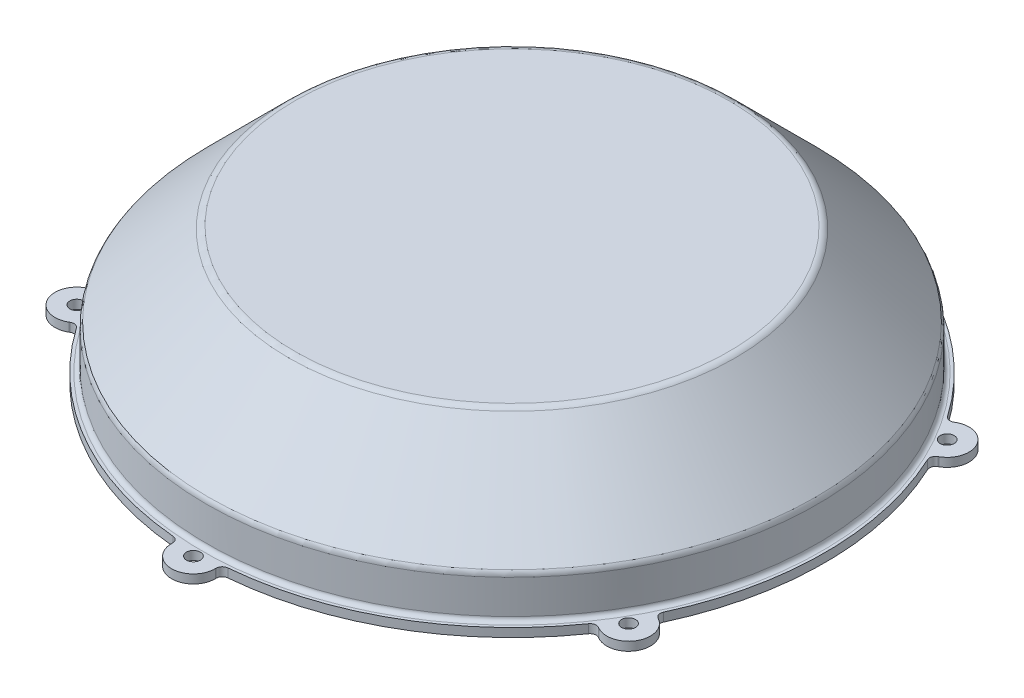
SolidWorks part; units mm, degrees
material "АБС-2020, черный"
ref_plane "Спереди" through (0, 0, 0) normal (0, 0, 1) x (1, 0, 0)
ref_plane "Сверху" through (0, 0, 0) normal (0, 1, 0) x (1, 0, 0)
ref_plane "Справа" through (0, 0, 0) normal (1, 0, 0) x (0, 0, -1)
other "Configuration Table"
sketch "Эскиз1" plane through (0, 0, 0) normal (0, 1, 0) x (1, 0, 0)
  circle A0 centre (0, 0) radius 70
  circle A1 centre (0, 0) radius 67.5
  dimension "D1" = 140
  dimension "D2" = 135
extrude "Бобышка-Вытянуть1" add sketch "Эскиз1" along normal blind 10
sketch "Эскиз2" plane through (0, 0, 0) normal (0, -1, 0) x (1, 0, 0)
  line L0 (0, 0) -> (0, 68.2261) construction
  line L1 (-5, 73) -> (-5, 72.7838)
  line L2 (60.7199, 40.8301) -> (60.5327, 40.722)
  line L3 (5, 72.7838) -> (5, 73)
  line L4 (0, 69.7236) -> (0, 91.161) construction
  line L5 (65.5327, 32.0618) -> (65.7199, 32.1699)
  line L6 (65.7199, -32.1699) -> (65.5327, -32.0618)
  line L7 (60.5327, -40.722) -> (60.7199, -40.8301)
  line L8 (5, -73) -> (5, -72.7838)
  line L9 (-5, -72.7838) -> (-5, -73)
  line L10 (-60.7199, -40.8301) -> (-60.5327, -40.722)
  line L11 (-65.5327, -32.0618) -> (-65.7199, -32.1699)
  line L12 (-65.7199, 32.1699) -> (-65.5327, 32.0618)
  line L13 (-60.5327, 40.722) -> (-60.7199, 40.8301)
  arc A0 (5, 73) -> (-5, 73) centre (0, 73) ccw
  circle A1 centre (0, 0) radius 67.5
  arc A2 (-6.2774, 71.3892) -> (-58.6862, 41.131) centre (0, 0) ccw
  circle A3 centre (0, 73) radius 1.6
  arc A4 (65.7199, 32.1699) -> (60.7199, 40.8301) centre (63.2199, 36.5) ccw
  circle A5 centre (63.2199, 36.5) radius 1.6
  arc A6 (60.7199, -40.8301) -> (65.7199, -32.1699) centre (63.2199, -36.5) ccw
  circle A7 centre (63.2199, -36.5) radius 1.6
  arc A8 (-5, -73) -> (5, -73) centre (0, -73) ccw
  circle A9 centre (0, -73) radius 1.6
  arc A10 (-65.7199, -32.1699) -> (-60.7199, -40.8301) centre (-63.2199, -36.5) ccw
  circle A11 centre (-63.2199, -36.5) radius 1.6
  arc A12 (-60.7199, 40.8301) -> (-65.7199, 32.1699) centre (-63.2199, 36.5) ccw
  circle A13 centre (-63.2199, 36.5) radius 1.6
  arc A14 (58.6862, 41.131) -> (6.2774, 71.3892) centre (0, 0) ccw
  arc A15 (64.9636, -30.2583) -> (64.9636, 30.2583) centre (0, 0) ccw
  arc A16 (-58.6862, -41.131) -> (-6.2774, -71.3892) centre (0, 0) ccw
  arc A17 (6.2774, -71.3892) -> (58.6862, -41.131) centre (0, 0) ccw
  arc A18 (-64.9636, 30.2583) -> (-64.9636, -30.2583) centre (0, 0) ccw
  arc A19 (-5, 72.7838) -> (-6.2774, 71.3892) centre (-6.4, 72.7838) cw
  arc A20 (-60.5327, 40.722) -> (-58.6862, 41.131) centre (-59.8327, 41.9345) ccw
  arc A21 (-65.5327, 32.0618) -> (-64.9636, 30.2583) centre (-66.2327, 30.8494) cw
  arc A22 (-65.5327, -32.0618) -> (-64.9636, -30.2583) centre (-66.2327, -30.8494) ccw
  arc A23 (-60.5327, -40.722) -> (-58.6862, -41.131) centre (-59.8327, -41.9345) cw
  arc A24 (-5, -72.7838) -> (-6.2774, -71.3892) centre (-6.4, -72.7838) ccw
  arc A25 (5, -72.7838) -> (6.2774, -71.3892) centre (6.4, -72.7838) cw
  arc A26 (60.5327, -40.722) -> (58.6862, -41.131) centre (59.8327, -41.9345) ccw
  arc A27 (65.5327, -32.0618) -> (64.9636, -30.2583) centre (66.2327, -30.8494) cw
  arc A28 (65.5327, 32.0618) -> (64.9636, 30.2583) centre (66.2327, 30.8494) ccw
  arc A29 (60.5327, 40.722) -> (58.6862, 41.131) centre (59.8327, 41.9345) cw
  arc A30 (6.2774, 71.3892) -> (5, 72.7838) centre (6.4, 72.7838) cw
  point P45 (0, 0)
  dimension "D1" = 10
  dimension "D2" = 3.2
  dimension "D4" = 1.4
  dimension "D3" = 135
  dimension "D5" = 73
extrude "Бобышка-Вытянуть2" add sketch "Эскиз2" along normal blind 2
fillet "Скругление1" radius 1 1 edges at (0, 0, -70)
sketch "Эскиз3" plane through (0, 0, 0) normal (0, 0, 1) x (1, 0, 0)
  line L0 (-69.5846, 10) -> (-50.5846, 29)
  line L1 (-50.5846, 29) -> (0, 29)
  line L2 (0, 29) -> (0, 27)
  line L3 (0, 27) -> (-49.7562, 27)
  line L4 (-49.7562, 27) -> (-66.7562, 10)
  line L5 (67.5, 10) -> (-67.5, 10) construction
  line L6 (-66.7562, 10) -> (-69.5846, 10)
  line L7 (70, 10) -> (-70, 10) construction
  line L8 (0, 27) -> (0, 0) construction
  dimension "D1" = 45
  dimension "D2" = 19
  dimension "D3" = 2
  dimension "D4" = 2
revolve "Повернуть1" add sketch "Эскиз3" angle 360 about L8
fillet "Скругление2" radius 2 2 edges at (-50.5846, 29, 0) (0, 10, 70)
